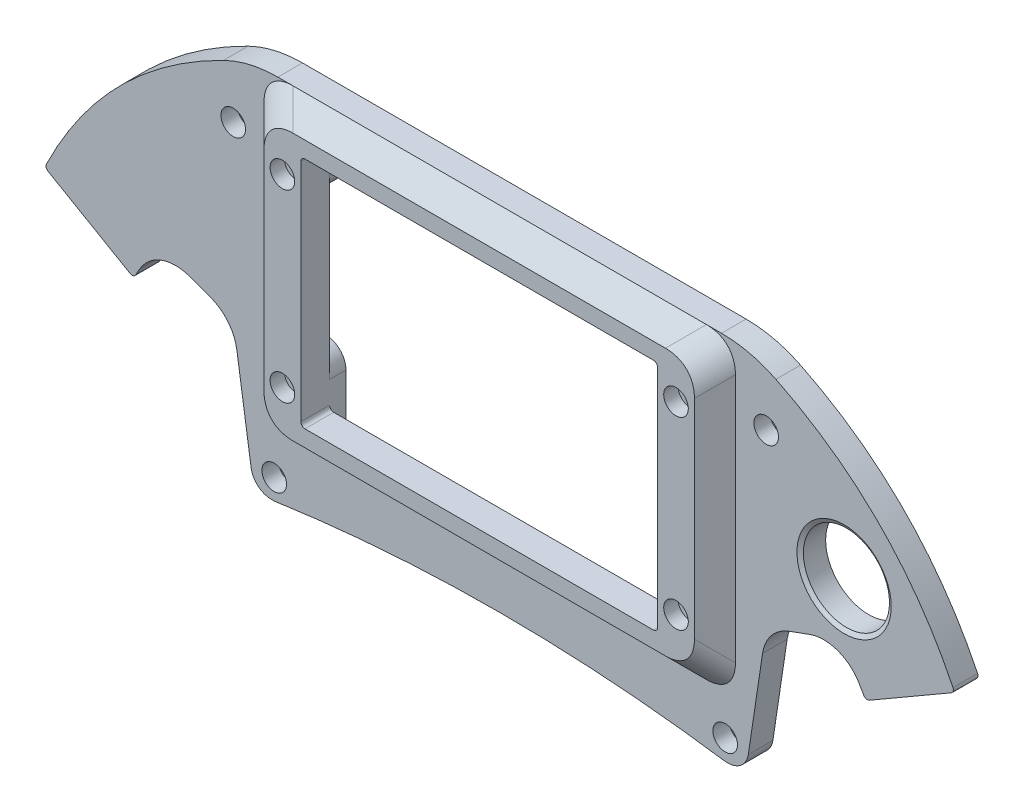
SolidWorks part; units mm, degrees
material "ABS"
ref_plane "正面" through (0, 0, 0) normal (0, 0, 1) x (1, 0, 0)
ref_plane "平面" through (0, 0, 0) normal (0, 1, 0) x (1, 0, 0)
ref_plane "右側面" through (0, 0, 0) normal (1, 0, 0) x (0, 0, -1)
sketch "ｽｹｯﾁ1" plane through (0, 0, 0) normal (0, 0, 1) x (1, 0, 0)
  line L1 (125, 105) -> (-125, 105) construction
  line L2 (125, 105) -> (125, -105) construction
  line L3 (125, -105) -> (-125, -105) construction
  line L4 (-125, 105) -> (-125, -105) construction
  line L5 (125, 105) -> (-125, -105) construction
  line L6 (125, -105) -> (-125, 105) construction
  circle A0 centre (0, 0) radius 125 construction
  point P0 (0, 0)
  dimension "D3" = 250
  dimension "D1" = 250
  dimension "D2" = 210
ref_plane "平面1" through (0, 0, 0) normal (0, 0, 1) x (1, 0, 0)
sketch "ｽｹｯﾁ2" plane through (0, 0, 0) normal (0, 0, 1) x (1, 0, 0)
  line L0 (0, 45) -> (-38.9711, -22.5) construction
  line L1 (-38.9711, -22.5) -> (38.9711, -22.5) construction
  line L2 (38.9711, -22.5) -> (0, 45) construction
  line L3 (-21.6506, 12.5) -> (21.6506, 12.5) construction
  line L4 (21.6506, 12.5) -> (0, -25) construction
  line L5 (0, -25) -> (-21.6506, 12.5) construction
  circle A0 centre (0, 0) radius 45 construction
  circle A1 centre (0, 0) radius 30 construction
  circle A2 centre (0, 0) radius 25 construction
  arc A3 (-29.9898, -0.784) -> (-15.6738, -25.5799) centre (-38.9711, -22.5) cw construction
  arc A4 (15.6738, -25.5799) -> (29.9898, -0.784) centre (38.9711, -22.5) cw construction
  arc A5 (-14.3159, 26.3639) -> (14.3159, 26.3639) centre (0, 45) ccw construction
  circle A6 centre (-21.6506, 12.5) radius 2.1 construction
  circle A7 centre (21.6506, 12.5) radius 2.1 construction
  circle A8 centre (0, -25) radius 2.1 construction
  dimension "D1" = 90
  dimension "D2" = 60
  dimension "D3" = 50
  dimension "D4" = 23.5
  dimension "D5" = 23.5
  dimension "D6" = 23.5
  dimension "D7" = 4.2
  dimension "D8" = 4.2
  dimension "D9" = 4.2
sketch "ｽｹｯﾁ3" plane through (0, 0, 0) normal (0, 0, 1) x (1, 0, 0)
  line L0 (-125, 105) -> (-125, -105) construction
  line L1 (125, 105) -> (125, -105) construction
  line L2 (-114.5644, 50) -> (114.5644, 50) construction
  line L3 (-105, -100) -> (-75, -100) construction
  line L4 (125, -105) -> (-125, -105) construction
  line L5 (0, 105) -> (0, -105) construction
  line L6 (125, 105) -> (-125, 105) construction
  line L7 (105, -100) -> (75, -100) construction
  arc A0 (-114.5644, 50) -> (-125, 0) centre (0, 0) ccw construction
  circle A1 centre (0, 0) radius 125 construction
  arc A2 (114.5644, 50) -> (125, 0) centre (0, 0) cw construction
  arc A3 (-95, 0) -> (-80.7775, 50) centre (0, 0) cw construction
  arc A4 (114.5644, 50) -> (125, 0) centre (0, 0) cw construction
  arc A5 (95, 0) -> (80.7775, 50) centre (0, 0) ccw construction
  spline S0 degree 3 poles (-125, 0) (-125, -34.2165) (-117.8201, -68.3401) (-105, -100) knots 0 0 0 0 1 1 1 1 construction
  spline S1 degree 3 poles (-75, -100) (-87.8201, -67.9365) (-95, -34.605) (-95, 0) knots 0 0 0 0 1 1 1 1 construction
  spline S2 degree 3 poles (125, 0) (125, -34.2165) (117.8201, -68.3401) (105, -100) knots 0 0 0 0 1 1 1 1 construction
  spline S3 degree 3 poles (75, -100) (87.8201, -67.9365) (95, -34.605) (95, 0) knots 0 0 0 0 1 1 1 1 construction
  point P12 (-120, -50)
  point P13 (-105, -100)
  point P18 (-90, -50)
  point P20 (-95, 0)
  dimension "D1" = 50
  dimension "D2" = 100
  dimension "D9" = 50
  dimension "D3" = 50
  dimension "D4" = 20
  dimension "D5" = 5
  dimension "D6" = 30
  dimension "D7" = 30
  dimension "D8" = 30
  dimension "D10" = 105
sketch "ｽｹｯﾁ4" plane through (0, 0, 0) normal (0, 0, 1) x (1, 0, 0)
  line L5 (125, -105) -> (-125, -105) construction
  line L8 (0, 105) -> (0, -105) construction
  line L10 (-125, 0) -> (125, 0) construction
  line L19 (0, -105) -> (0, 105) construction
  circle A0 centre (0, 0) radius 30 construction
  spline S2 degree 3 poles (-105, -100) (-71.8006, -85.9254) (0, -74.0746) (71.8006, -85.9254) (105, -100) knots 0 0 0 0 0.5 1 1 1 1 construction
  point P21 (-55, -85)
  point P22 (0, -80)
  point P23 (55, -85)
  point P58 (0, 30)
  dimension "D7" = 25
  dimension "D8" = 20
  dimension "D9" = 20
  dimension "D10" = 55
  dimension "D11" = 55
sketch "ｽｹｯﾁ5" plane through (0, 0, 0) normal (0, 0, 1) x (1, 0, 0)
  line L0 (-14.3159, 26.3639) -> (14.3159, 26.3639) construction
  circle A0 centre (0, 0) radius 100 construction
  dimension "D1" = 200
sketch "ｽｹｯﾁ6" plane through (0, 0, 0) normal (0, 0, 1) x (1, 0, 0)
  line L0 (0, -105) -> (0, 105) construction
  line L1 (-52.5, 98) -> (52.5, 98) construction
  line L2 (-52.5, 98) -> (-52.5, 28) construction
  line L3 (-52.5, 28) -> (52.5, 28) construction
  line L4 (52.5, 98) -> (52.5, 28) construction
  line L5 (-52.5, 98) -> (52.5, 28) construction
  line L6 (-52.5, 28) -> (52.5, 98) construction
  line L7 (125, 105) -> (-125, 105) construction
  point P0 (0, 63)
  dimension "D1" = 70
  dimension "D2" = 105
  dimension "D3" = 7
sketch "ｽｹｯﾁ7" plane through (0, 0, 0) normal (0, 0, 1) x (1, 0, 0)
  line L0 (-100, 0) -> (-60, 0) construction
  line L1 (-125, 0) -> (125, 0) construction
  line L2 (-98.8686, 15) -> (-60, 15) construction
  line L3 (-60, 15) -> (-65, 48.2606) construction
  line L4 (-65, 48.2606) -> (-83.5165, 55) construction
  line L5 (-60, 15) -> (-41.9606, -105) construction
  line L6 (125, -105) -> (-125, -105) construction
  line L7 (-60, -5) -> (-56.9934, -5) construction
  line L8 (-125, 105) -> (-125, -105) construction
  line L9 (-83.5165, 55) -> (-89.3029, 45) construction
  line L10 (-89.3029, 45) -> (-110.9703, 57.5377) construction
  line L11 (-110.9703, 57.5377) -> (-92.9863, 83.5377) construction
  line L12 (-92.9863, 83.5377) -> (-60.5, 105) construction
  line L13 (125, 105) -> (-125, 105) construction
  line L14 (-73.1949, -68.1359) -> (-48.3047, -62.7982) construction
  line L15 (-99.8749, -5) -> (-60, -5) construction
  line L16 (0, 0) -> (0, -30) construction
  line L17 (0, -105) -> (0, 105) construction
  line L18 (73.1949, -68.1359) -> (48.3047, -62.7982) construction
  line L19 (60, 15) -> (41.9606, -105) construction
  line L20 (60, -5) -> (56.9934, -5) construction
  line L21 (99.8749, -5) -> (60, -5) construction
  line L22 (98.8686, 15) -> (60, 15) construction
  line L23 (60, 15) -> (65, 48.2606) construction
  line L24 (65, 48.2606) -> (83.5165, 55) construction
  line L25 (83.5165, 55) -> (89.3029, 45) construction
  line L26 (89.3029, 45) -> (110.9703, 57.5377) construction
  line L27 (110.9703, 57.5377) -> (92.9863, 83.5377) construction
  line L28 (92.9863, 83.5377) -> (60.5, 105) construction
  circle A0 centre (0, 0) radius 100 construction
  circle A1 centre (0, 0) radius 125 construction
  arc A2 (-105, -100) -> (105, -100) centre (0, -348.7469) cw construction
  circle A3 centre (0, -348.7469) radius 270 construction
  circle A4 centre (0, -433.417) radius 132.7909 construction
  circle A5 centre (0, -348.7469) radius 290 construction
  circle A6 centre (0, 0) radius 30 construction
  spline S0 degree 3 poles (-105, -100) (-71.8006, -85.9254) (0, -74.0746) (71.8006, -85.9254) (105, -100) knots 0 0 0 0 0.5 1 1 1 1 construction
  dimension "D12" = 540
  dimension "D13" = 580
  dimension "D1" = 40
  dimension "D2" = 15
  dimension "D3" = 40
  dimension "D4" = 40
  dimension "D5" = 20
  dimension "D6" = 60
  dimension "D7" = 10
  dimension "D8" = 26
  dimension "D9" = 8
  dimension "D10" = 5
  dimension "D11" = 40
sketch "ｽｹｯﾁ8" plane through (0, 0, 0) normal (0, 0, 1) x (1, 0, 0)
  line L0 (-60, 15) -> (-65, 48.2606)
  line L1 (-65, 48.2606) -> (-83.5165, 55)
  line L2 (-83.5165, 55) -> (-89.3029, 45)
  line L3 (-89.3029, 45) -> (-110.9703, 57.5377)
  line L6 (-60.5, 105) -> (60.5, 105)
  line L9 (110.9703, 57.5377) -> (89.3029, 45)
  line L10 (89.3029, 45) -> (83.5165, 55)
  line L11 (83.5165, 55) -> (65, 48.2606)
  line L12 (65, 48.2606) -> (60, 15)
  line L13 (-60, 15) -> (-30, 10)
  line L14 (-30, 10) -> (30, 10) construction
  line L15 (-52.5, 98) -> (52.5, 28) construction
  line L16 (52.5, 98) -> (-52.5, 98)
  line L17 (52.5, 98) -> (52.5, 28)
  line L18 (52.5, 28) -> (-52.5, 28)
  line L19 (-52.5, 98) -> (-52.5, 28)
  line L20 (52.5, 98) -> (-52.5, 28) construction
  line L21 (52.5, 28) -> (-52.5, 98) construction
  line L22 (30, 10) -> (60, 15)
  line L23 (-125, 105) -> (-125, -105) construction
  line L24 (125, 105) -> (125, -105) construction
  line L25 (-125, 0) -> (125, 0) construction
  line L26 (-30, 10) -> (-26.6506, 10)
  line L27 (-26.6506, 10) -> (-26.6506, 12.5)
  line L28 (-16.6506, 12.5) -> (-16.6506, 10)
  line L29 (-16.6506, 10) -> (16.6506, 10)
  line L30 (16.6506, 10) -> (16.6506, 12.5)
  line L31 (26.6506, 12.5) -> (26.6506, 10)
  line L32 (26.6506, 10) -> (30, 10)
  circle A0 centre (-21.6506, 12.5) radius 5 construction
  circle A1 centre (21.6506, 12.5) radius 5 construction
  arc A2 (-26.6506, 12.5) -> (-16.6506, 12.5) centre (-21.6506, 12.5) cw
  arc A3 (16.6506, 12.5) -> (26.6506, 12.5) centre (21.6506, 12.5) cw
  spline S0 degree 2 poles (-110.9703, 57.5377) (-95.1002, 90.8355) (-60.5, 105) knots 0 0 0 1 1 1
  spline S1 degree 2 poles (110.9703, 57.5377) (95.1002, 90.8355) (60.5, 105) knots 0 0 0 1 1 1
  point P22 (0, 63)
  dimension "D4" = 10
  dimension "D5" = 10
  dimension "D1" = 95
  dimension "D2" = 95
  dimension "D3" = 10
extrude "ﾎﾞｽ - 押し出し1" add sketch "ｽｹｯﾁ8" along normal blind 6 contours L30 A3 L31 L32 L22 L12 L11 L10 L9 L6 L3 L2 L1 L0 L13 L26 L27 A2 L28 L29 L19 L16 L17 L18 region at (-60.1126, 31.9892, 0)
sketch "ｽｹｯﾁ9" plane through (0, 0, 6) normal (0, 0, 1) x (1, 0, 0)
  line L0 (-52.5, 73) -> (-46.5, 65.8495) construction
  line L1 (-52.5, 98) -> (-52.5, 28) construction
  line L2 (-46.5, 65.8495) -> (-46.5, 28) construction
  line L3 (-52.5, 28) -> (52.5, 28) construction
  line L4 (52.5, 73) -> (46.5, 65.8495) construction
  line L5 (52.5, 98) -> (52.5, 28) construction
  line L6 (46.5, 65.8495) -> (46.5, 28) construction
  dimension "D1" = 25
  dimension "D2" = 25
  dimension "D3" = 6
  dimension "D4" = 6
  dimension "D5" = 40
  dimension "D6" = 40
sketch "ｽｹｯﾁ11" plane through (0, 0, 6) normal (0, 0, 1) x (1, 0, 0)
  line L0 (0, -105) -> (0, 105) construction
  line L1 (-42.5, 95) -> (42.5, 95) construction
  line L2 (-42.5, 95) -> (-42.5, 40) construction
  line L3 (-42.5, 40) -> (42.5, 40) construction
  line L4 (42.5, 95) -> (42.5, 40) construction
  line L5 (-42.5, 95) -> (42.5, 40) construction
  line L6 (-42.5, 40) -> (42.5, 95) construction
  line L7 (-52.5, 28) -> (52.5, 28) construction
  line L9 (0, 26) -> (-54.5, 26) construction
  line L10 (-54.5, 26) -> (-54.5, 100) construction
  line L11 (-54.5, 100) -> (54.5, 100) construction
  line L12 (54.5, 100) -> (54.5, 26) construction
  line L13 (54.5, 26) -> (0, 26) construction
  line L14 (-52.5, 98) -> (-52.5, 28) construction
  line L15 (-52.5, 98) -> (52.5, 98) construction
  line L16 (52.5, 98) -> (52.5, 28) construction
  point P0 (0, 67.5)
  dimension "D1" = 85
  dimension "D2" = 55
  dimension "D3" = 3
  dimension "D4" = 2
  dimension "D5" = 2
  dimension "D6" = 2
  dimension "D7" = 2
sketch "ｽｹｯﾁ12" plane through (0, 0, 6) normal (0, 0, 1) x (1, 0, 0)
  line L0 (-42.5, 40) -> (42.5, 40)
  line L1 (42.5, 40) -> (42.5, 95)
  line L2 (42.5, 95) -> (-42.5, 95)
  line L3 (-42.5, 95) -> (-42.5, 40)
  line L4 (-54.5, 26) -> (54.5, 26)
  line L5 (54.5, 26) -> (54.5, 100)
  line L6 (54.5, 100) -> (-54.5, 100)
  line L7 (-54.5, 100) -> (-54.5, 26)
extrude "ﾎﾞｽ - 押し出し2" add sketch "ｽｹｯﾁ12" along normal blind 7 and the other way blind 2
sketch "ｽｹｯﾁ13" plane through (0, 0, 13) normal (0, 0, 1) x (1, 0, 0)
  line L1 (-58.5, 77.0391) -> (-58.5, 25.0391)
  line L2 (-58.5, 25.0391) -> (-48.5, 25.0391)
  line L5 (58.5, 77.0391) -> (58.5, 25.0391)
  line L6 (58.5, 25.0391) -> (48.5, 25.0391)
  line L11 (58.5, 77.0391) -> (48.5, 65.1215)
  line L12 (48.5, 65.1215) -> (48.5, 25.0391)
  line L13 (52.5, 73) -> (46.5, 65.8495) construction
  line L15 (46.5, 65.8495) -> (46.5, 28) construction
  line L16 (-58.5, 77.0391) -> (-48.5, 65.1215)
  line L17 (-48.5, 65.1215) -> (-48.5, 25.0391)
  line L18 (-52.5, 73) -> (-46.5, 65.8495) construction
  line L20 (-46.5, 65.8495) -> (-46.5, 28) construction
  point P14 (49.5, 69.4247)
  dimension "D1" = 2
  dimension "D2" = 52
  dimension "D3" = 10
  dimension "D4" = 52
  dimension "D5" = 2
  dimension "D6" = 2
  dimension "D7" = 2
  dimension "D8" = 10
extrude "ｶｯﾄ - 押し出し1" cut sketch "ｽｹｯﾁ13" against normal blind 7
sketch "ｽｹｯﾁ14" plane through (0, 0, 0) normal (0, 0, 1) x (1, 0, 0)
  line L0 (-52.5, 98) -> (52.5, 98) construction
  line L1 (-52.5, 98) -> (-52.5, 28) construction
  line L3 (0, 67.5) -> (0, 46.8637) construction
  line L4 (-42.5, 95) -> (42.5, 40) construction
  line L5 (0, -105) -> (0, 105) construction
  circle A0 centre (-48.5, 76) radius 3 construction
  circle A2 centre (48.5, 76) radius 3 construction
  circle A3 centre (48.5, 76) radius 1.75
  circle A4 centre (-48.5, 76) radius 1.75
  dimension "D1" = 6
  dimension "D4" = 3.5
  dimension "D5" = 3.5
  dimension "D2" = 22
  dimension "D3" = 4
sketch "ｽｹｯﾁ15" plane through (0, 0, 4) normal (0, 0, -1) x (-1, 0, 0)
  line L0 (-52.5, 80) -> (-43.5, 80)
  line L1 (-52.5, 98) -> (-52.5, 28) construction
  line L2 (-43.5, 80) -> (-43.5, 72)
  line L5 (-43.5, 72) -> (-51.6609, 72)
  line L6 (-52.5, 73) -> (-46.5, 65.8495) construction
  line L7 (-51.6609, 72) -> (-46.5, 65.8495)
  line L8 (-46.5, 65.8495) -> (-46.5, 28)
  line L9 (-46.5, 28) -> (46.5, 28)
  line L10 (46.5, 28) -> (46.5, 65.8495)
  line L11 (46.5, 65.8495) -> (51.6609, 72)
  line L12 (52.5, 73) -> (46.5, 65.8495) construction
  line L13 (51.6609, 72) -> (42.5, 72)
  line L14 (42.5, 72) -> (42.5, 80)
  line L15 (42.5, 80) -> (52.5, 80)
  line L16 (52.5, 98) -> (52.5, 28) construction
  line L17 (42.5, 95) -> (42.5, 40) construction
  line L18 (52.5, 80) -> (52.5, 98)
  line L19 (52.5, 98) -> (-52.5, 98)
  line L20 (-52.5, 98) -> (-52.5, 80)
  circle A0 centre (-48.5, 76) radius 3 construction
  dimension "D1" = 4
  dimension "D2" = 4
  dimension "D3" = 5
  dimension "D4" = 8
  dimension "D5" = 4
extrude "ｶｯﾄ - 押し出し2" cut sketch "ｽｹｯﾁ15" against normal blind 7
extrude "ｶｯﾄ - 押し出し4" cut sketch "ｽｹｯﾁ14" along normal blind 100
sketch "ｽｹｯﾁ16" plane through (0, 0, 13) normal (0, 0, 1) x (1, 0, 0)
  circle A0 centre (48.5, 76) radius 3
  circle A1 centre (-48.5, 76) radius 3
  dimension "D1" = 6
  dimension "D2" = 6
extrude "ｶｯﾄ - 押し出し5" cut sketch "ｽｹｯﾁ16" against normal blind 3.5
sketch "ｽｹｯﾁ17" plane through (0, 0, 4) normal (0, 0, -1) x (-1, 0, 0)
  line L0 (-43.5, 72) -> (-52.5, 72)
  line L1 (-52.5, 98) -> (-52.5, 28) construction
  line L2 (-52.5, 72) -> (-52.5, 80)
  line L3 (-52.5, 80) -> (-43.5, 80)
  line L6 (43.5, 72) -> (52.5, 72)
  line L7 (52.5, 98) -> (52.5, 28) construction
  line L8 (52.5, 72) -> (52.5, 80)
  line L9 (52.5, 80) -> (43.5, 80)
  line L10 (-43.5, 72) -> (-51.6609, 72) construction
  line L11 (-43.5, 80) -> (-43.5, 72)
  line L12 (-43.5, 80) -> (-43.5, 72) construction
  line L14 (51.6609, 72) -> (42.5, 72) construction
  line L15 (42.5, 80) -> (52.5, 80) construction
  line L16 (43.5, 80) -> (43.5, 72)
  dimension "D1" = 9
extrude "ｶｯﾄ - 押し出し6" cut sketch "ｽｹｯﾁ17" against normal blind 3
sketch "ｽｹｯﾁ18" plane through (0, 0, 11) normal (0, 0, -1) x (-1, 0, 0)
  line L0 (52.5, 98) -> (-52.5, 98) construction
  line L1 (-52.5, 98) -> (-52.5, 28) construction
  circle A0 centre (-41.25, 92) radius 2.6
  circle A1 centre (-33.75, 92) radius 2.6
  circle A2 centre (-26.25, 92) radius 2.6
  circle A3 centre (-18.75, 92) radius 2.6
  circle A4 centre (-11.25, 92) radius 2.6
  circle A5 centre (-3.75, 92) radius 2.6
  circle A6 centre (3.75, 92) radius 2.6
  circle A7 centre (11.25, 92) radius 2.6
  circle A8 centre (18.75, 92) radius 2.6
  circle A9 centre (26.25, 92) radius 2.6
  circle A10 centre (33.75, 92) radius 2.6
  circle A11 centre (41.25, 92) radius 2.6
  dimension "D1" = 5.2
  dimension "D3" = 11.25
  dimension "D2" = 6
  dimension "D4" = 12
extrude "ｶｯﾄ - 押し出し7" cut sketch "ｽｹｯﾁ18" against normal blind 3
sketch "ｽｹｯﾁ19" plane through (0, 0, 6) normal (0, 0, 1) x (1, 0, 0)
  line L1 (-125, 0) -> (125, 0) construction
  line L2 (0, -105) -> (0, 105) construction
  circle A0 centre (84, 68) radius 10.5 construction
  dimension "D1" = 21
  dimension "D3" = 84
  dimension "D2" = 68
sketch "ｽｹｯﾁ21" plane through (0, 0, 6) normal (0, 0, 1) x (1, 0, 0)
  line L0 (83.0683, 57.5414) -> (83.5165, 55)
  line L1 (65, 48.2606) -> (83.5165, 55) construction
  line L2 (83.5165, 55) -> (86.3919, 42.8329)
  line L3 (86.3919, 42.8329) -> (125.4665, 52.0672)
  line L4 (125.4665, 52.0672) -> (98.7771, 79.0548)
  line L5 (98.7771, 79.0548) -> (92.6692, 73.9241)
  line L6 (125, 105) -> (-125, -105) construction
  arc A0 (83.0683, 57.5414) -> (92.6692, 73.9241) centre (84, 68) cw
  circle A1 centre (84, 68) radius 10.5 construction
  dimension "D1" = 100
  dimension "D2" = 3
sketch "ｽｹｯﾁ22" plane through (0, 0, 6) normal (0, 0, 1) x (1, 0, 0)
  circle A0 centre (84, 68) radius 10.5
  dimension "D1" = 21
sketch "ｽｹｯﾁ25" plane through (0, 0, 4) normal (0, 0, -1) x (-1, 0, 0)
  line L0 (42.5, 80) -> (43.5, 80)
  line L1 (42.5, 80) -> (43.5, 80) construction
  line L2 (43.5, 80) -> (43.5, 72)
  line L3 (43.5, 80) -> (43.5, 72) construction
  line L4 (43.5, 72) -> (42.5, 72)
  line L5 (42.5, 72) -> (42.5, 80)
extrude "ｶｯﾄ - 押し出し14" cut sketch "ｽｹｯﾁ25" against normal blind 7
sketch "ｽｹｯﾁ26" plane through (0, 0, 13) normal (0, 0, 1) x (1, 0, 0)
  line L1 (43.5, 96) -> (-43.5, 96)
  line L2 (43.5, 96) -> (43.5, 39)
  line L3 (43.5, 39) -> (-43.5, 39)
  line L4 (-43.5, 96) -> (-43.5, 39)
  line L5 (43.5, 96) -> (-43.5, 39) construction
  line L6 (43.5, 39) -> (-43.5, 96) construction
  point P0 (0, 67.5)
  dimension "D1" = 57
  dimension "D2" = 87
extrude "ｶｯﾄ - 押し出し15" cut sketch "ｽｹｯﾁ26" against normal blind 7
sketch "ｽｹｯﾁ27" plane through (0, 0, 4) normal (0, 0, -1) x (-1, 0, 0)
  line L0 (-52.5, 72) -> (-51.6609, 72)
  line L1 (-51.6609, 72) -> (-46.5, 65.8495)
  line L2 (-46.5, 65.8495) -> (-46.5, 28)
  line L3 (-46.5, 28) -> (-52.5, 28)
  line L5 (0, 30) -> (0, 45) construction
  line L6 (-52.5, 28) -> (-52.5, 72)
  line L7 (46.5, 28) -> (52.5, 28)
  line L8 (46.5, 65.8495) -> (46.5, 28)
  line L9 (51.6609, 72) -> (46.5, 65.8495)
  line L10 (52.5, 72) -> (51.6609, 72)
  line L11 (52.5, 28) -> (52.5, 72)
extrude "ﾎﾞｽ - 押し出し3" add sketch "ｽｹｯﾁ27" along normal blind 6
sketch "ｽｹｯﾁ29" plane through (0, 0, 6) normal (0, 0, 1) x (1, 0, 0)
  line L0 (125, 105) -> (-125, 105) construction
  line L1 (0, -105) -> (0, 105) construction
  line L2 (0, 67.5) -> (0, 26.3639) construction
  line L3 (-14.3159, 26.3639) -> (14.3159, 26.3639) construction
  circle A0 centre (-65, 90) radius 1.5 construction
  circle A1 centre (-55, 20) radius 1.5 construction
  circle A2 centre (65, 90) radius 1.5 construction
  circle A3 centre (55, 20) radius 1.5 construction
  dimension "D1" = 3
  dimension "D2" = 15
  dimension "D3" = 65
  dimension "D4" = 3
  dimension "D5" = 55
  dimension "D6" = 85
sketch "ｽｹｯﾁ30" plane through (0, 0, 6) normal (0, 0, 1) x (1, 0, 0)
  line L0 (0, 67.5) -> (0, 30) construction
  line L1 (-42.5, 40) -> (42.5, 95) construction
  circle A0 centre (-65, 90) radius 3
  circle A1 centre (-55, 20) radius 3
  circle A2 centre (55, 20) radius 3
  circle A3 centre (65, 90) radius 3
  dimension "D1" = 6
  dimension "D2" = 6
extrude "ｶｯﾄ - 押し出し16" cut sketch "ｽｹｯﾁ30" against normal blind 4
sketch "ｽｹｯﾁ31" plane through (0, 0, 6) normal (0, 0, 1) x (1, 0, 0)
  line L0 (0, 67.5) -> (0, 26) construction
  circle A0 centre (-65, 90) radius 1.75
  circle A1 centre (-55, 20) radius 1.75
  circle A2 centre (55, 20) radius 1.75
  circle A3 centre (65, 90) radius 1.75
  dimension "D1" = 3.5
  dimension "D2" = 3.5
extrude "ｶｯﾄ - 押し出し17" cut sketch "ｽｹｯﾁ31" against normal blind 50
sketch "ｽｹｯﾁ33" plane through (0, 0, 0) normal (0, 0, -1) x (-1, 0, 0)
  line L0 (106.6531, 58.5056) -> (90.5191, 81.8311)
  line L2 (84.8536, 58.6792) -> (90.397, 49.0991)
  line L3 (90.397, 49.0991) -> (106.6531, 58.5056)
  line L6 (83.5, 84) -> (57.5, 84)
  line L7 (57.5, 84) -> (57.5, 50.4323)
  line L8 (89.3029, 45) -> (110.9703, 57.5377) construction
  line L9 (83.5165, 55) -> (89.3029, 45) construction
  line L13 (90.5191, 81.8311) -> (83.5, 84)
  line L14 (52.5, 98) -> (52.5, 72) construction
  line L16 (84.8536, 58.6792) -> (62.1954, 50.4323)
  line L17 (62.1954, 50.4323) -> (57.5, 50.4323)
  line L18 (65, 48.2606) -> (83.5165, 55) construction
  line L19 (54.5, 26) -> (54.5, 100) construction
  line L20 (110.9703, 57.5377) -> (92.9863, 83.5377) construction
  line L21 (89.3029, 45) -> (110.9703, 57.5377) construction
  circle A2 centre (65, 90) radius 1.75 construction
  dimension "D1" = 6
  dimension "D2" = 3
  dimension "D3" = 3
  dimension "D4" = 3
  dimension "D5" = 3
  dimension "D6" = 3
  dimension "D7" = 3
  dimension "D8" = 26
sketch "ｽｹｯﾁ36" plane through (0, 0, 0) normal (0, 0, -1) x (-1, 0, 0)
  line L0 (-57.5, 50) -> (-57.5, 84)
  line L3 (-77.6828, 56.0692) -> (-61.0077, 50)
  line L4 (-61.0077, 50) -> (-57.5, 50)
  line L5 (-65, 48.2606) -> (-83.5165, 55) construction
  line L7 (-80.3599, 81) -> (-80.3599, 84)
  line L8 (-54.5, 100) -> (-54.5, 26) construction
  line L9 (-80.3599, 84) -> (-57.5, 84)
  line L10 (-98.8686, 15) -> (-60, 15) construction
  arc A0 (-80.3599, 81) -> (-77.6828, 56.0692) centre (-84, 68) cw
  circle A2 centre (-84, 68) radius 10.5 construction
  dimension "D1" = 3
  dimension "D4" = 6
  dimension "D3" = 3
  dimension "D2" = 3
  dimension "D5" = 3
  dimension "D6" = 35
sketch "ｽｹｯﾁ37" plane through (0, 0, 6) normal (0, 0, 1) x (1, 0, 0)
  line L0 (-60, 15) -> (-30, 15)
  line L1 (-30, 15) -> (-28.5566, 17.5)
  line L2 (-28.5566, 17.5) -> (28.5566, 17.5)
  line L3 (0, -105) -> (0, 105) construction
  line L4 (0, 17.5) -> (0, 0) construction
  line L5 (60, 0) -> (-60, 0)
  line L6 (-60, 0) -> (-60, 15)
  line L7 (30, 15) -> (28.5566, 17.5)
  line L8 (60, 15) -> (30, 15)
  line L9 (60, 0) -> (60, 15)
  arc A1 (-16.6506, 12.5) -> (-26.6506, 12.5) centre (-21.6506, 12.5) ccw construction
  dimension "D1" = 30
  dimension "D2" = 120
extrude "ｶｯﾄ - 押し出し18" cut sketch "ｽｹｯﾁ37" against normal blind 10
sketch "ｽｹｯﾁ38" plane through (0, 0, 6) normal (0, 0, 1) x (1, 0, 0)
  line L1 (153.4339, 129.5916) -> (-153.4339, 129.5916)
  line L2 (153.4339, 129.5916) -> (153.4339, 5.4084)
  line L3 (153.4339, 5.4084) -> (-153.4339, 5.4084)
  line L4 (-153.4339, 129.5916) -> (-153.4339, 5.4084)
  line L5 (153.4339, 129.5916) -> (-153.4339, 5.4084) construction
  line L6 (153.4339, 5.4084) -> (-153.4339, 129.5916) construction
  point P0 (0, 67.5)
extrude "ｶｯﾄ - 押し出し19" cut sketch "ｽｹｯﾁ38" along normal blind 10
sketch "ｽｹｯﾁ39" plane through (0, 0, 6) normal (0, 0, 1) x (1, 0, 0)
  line L0 (-52.5, 98) -> (52.5, 98)
  line L1 (52.5, 98) -> (52.5, 28)
  line L2 (52.5, 28) -> (-52.5, 28)
  line L3 (-52.5, 28) -> (-52.5, 98)
extrude "ﾎﾞｽ - 押し出し4" add sketch "ｽｹｯﾁ39" against normal blind 8
sketch "ｽｹｯﾁ40" plane through (0, 0, 6) normal (0, 0, 1) x (1, 0, 0)
  line L0 (0, -105) -> (0, 105) construction
  line L1 (52.5, 100) -> (-52.5, 100)
  line L2 (52.5, 100) -> (52.5, 35)
  line L3 (52.5, 35) -> (-52.5, 35)
  line L4 (-52.5, 100) -> (-52.5, 35)
  line L5 (52.5, 100) -> (-52.5, 35) construction
  line L6 (52.5, 35) -> (-52.5, 100) construction
  line L11 (-42.5, 40) -> (42.5, 40) construction
  point P0 (0, 67.5)
  dimension "D1" = 105
  dimension "D2" = 65
  dimension "D3" = 5
sketch "ｽｹｯﾁ42" plane through (0, 0, 6) normal (0, 0, 1) x (1, 0, 0)
  line L0 (0, -105) -> (0, 105) construction
  line L1 (-57.5, 105) -> (57.5, 105)
  line L2 (-57.5, 105) -> (-57.5, 30)
  line L3 (-57.5, 30) -> (57.5, 30)
  line L4 (57.5, 105) -> (57.5, 30)
  line L5 (-57.5, 105) -> (57.5, 30) construction
  line L6 (-57.5, 30) -> (57.5, 105) construction
  line L7 (125, 105) -> (-125, 105) construction
  line L9 (52.5, 35) -> (-52.5, 35) construction
  point P0 (0, 67.5)
  dimension "D1" = 115
  dimension "D2" = 5
ref_plane "平面2" through (0, 0, 11) normal (0, 0, 1) x (1, 0, 0)
sketch "ｽｹｯﾁ43" plane through (0, 0, 11) normal (0, 0, 1) x (1, 0, 0)
  line L0 (-57.5, 105) -> (57.5, 30) construction
  line L1 (52.5, 100) -> (-52.5, 100)
  line L2 (52.5, 100) -> (52.5, 35)
  line L3 (52.5, 35) -> (-52.5, 35)
  line L4 (-52.5, 100) -> (-52.5, 35)
  line L5 (52.5, 100) -> (-52.5, 35) construction
  line L6 (52.5, 35) -> (-52.5, 100) construction
  point P0 (0, 67.5)
  dimension "D1" = 105
  dimension "D2" = 65
loft "ﾛﾌﾄ1" add profiles "ｽｹｯﾁ43", "ｽｹｯﾁ42" connector at (-52.5, 100, 11) connector at (-57.5, 105, 6)
fillet "ﾌｨﾚｯﾄ1" radius 10 4 edges
sketch "ｽｹｯﾁ44" plane through (0, 0, 11) normal (0, 0, 1) x (1, 0, 0)
  line L1 (43.5, 96) -> (-43.5, 96)
  line L2 (43.5, 96) -> (43.5, 39)
  line L3 (43.5, 39) -> (-43.5, 39)
  line L4 (-43.5, 96) -> (-43.5, 39)
  line L5 (43.5, 96) -> (-43.5, 39) construction
  line L6 (43.5, 39) -> (-43.5, 96) construction
  point P0 (0, 67.5)
  dimension "D1" = 87
  dimension "D2" = 57
extrude "ｶｯﾄ - 押し出し21" cut sketch "ｽｹｯﾁ44" against normal through all
sketch "ｽｹｯﾁ45" plane through (0, 0, 0) normal (0, 0, 1) x (1, 0, 0)
  line L0 (-48, 90) -> (-48, 45) construction
  line L2 (-43.5, 96) -> (-43.5, 39) construction
  line L3 (-54.5, 100) -> (54.5, 100) construction
  line L4 (52.5, 35) -> (-52.5, 35) construction
  line L5 (0, 105) -> (0, 30) construction
  circle A0 centre (-48, 90) radius 1.75
  circle A1 centre (-48, 45) radius 1.75
  circle A2 centre (48, 45) radius 1.75
  circle A3 centre (48, 90) radius 1.75
  dimension "D1" = 3.5
  dimension "D2" = 3.5
  dimension "D4" = 10
  dimension "D5" = 10
  dimension "D3" = 4.5
extrude "ｶｯﾄ - 押し出し23" cut sketch "ｽｹｯﾁ45" along normal through all
sketch "ｽｹｯﾁ46" plane through (0, 0, 11) normal (0, 0, 1) x (1, 0, 0)
  line L0 (0, 105) -> (0, 30) construction
  line L1 (125, 105) -> (-125, 105) construction
  circle A0 centre (-48, 90) radius 3
  circle A1 centre (-48, 45) radius 3
  circle A2 centre (48, 45) radius 3
  circle A3 centre (48, 90) radius 3
  dimension "D1" = 6
  dimension "D2" = 6
extrude "ｶｯﾄ - 押し出し24" cut sketch "ｽｹｯﾁ46" against normal blind 3.5
sketch "ｽｹｯﾁ47" plane through (0, 0, 0) normal (0, 0, -1) x (-1, 0, 0)
  circle A0 centre (-84, 68) radius 10.5
  dimension "D1" = 21
extrude "ｶｯﾄ - 押し出し25" cut sketch "ｽｹｯﾁ47" against normal through all
sketch "ｽｹｯﾁ48" plane through (0, 0, 0) normal (0, 0, -1) x (-1, 0, 0)
  line L0 (-84, 80.5) -> (-84, 84)
  line L1 (-84, 84) -> (-43.5, 84)
  line L2 (-43.5, 39) -> (-43.5, 96) construction
  line L3 (-43.5, 84) -> (-43.5, 51)
  line L4 (-43.5, 51) -> (-63.7551, 51)
  line L5 (-63.7551, 51) -> (-78.9936, 56.5463)
  line L6 (-65, 48.2606) -> (-83.5165, 55) construction
  line L7 (43.5, 84) -> (83.5, 84)
  line L8 (43.5, 96) -> (43.5, 39) construction
  line L9 (83.5, 84) -> (90.5191, 81.8311)
  line L10 (90.5191, 81.8311) -> (106.6531, 58.5056)
  line L11 (106.6531, 58.5056) -> (90.397, 49.0991)
  line L12 (90.397, 49.0991) -> (84.8536, 58.6792)
  line L13 (84.8536, 58.6792) -> (62.1954, 50.4323)
  line L14 (62.1954, 50.4323) -> (57.5, 50.4323)
  line L15 (43.5, 50.4323) -> (43.5, 84)
  line L16 (43.5, 50.4323) -> (57.5, 50.4323)
  arc A0 (-84, 80.5) -> (-78.9936, 56.5463) centre (-84, 68) cw
  circle A1 centre (-48, 45) radius 1.75 construction
  circle A2 centre (-48, 90) radius 1.75 construction
  dimension "D1" = 12.5
  dimension "D2" = 6
  dimension "D3" = 6
  dimension "D4" = 3
extrude "ｶｯﾄ - 押し出し26" cut sketch "ｽｹｯﾁ48" against normal blind 4
sketch "ｽｹｯﾁ49" plane through (0, 0, 0) normal (0, 0, -1) x (-1, 0, 0)
  line L0 (-43.5, 96) -> (-43.5, 101)
  line L1 (-43.5, 101) -> (43.5, 101)
  line L2 (43.5, 101) -> (43.5, 21.5)
  line L3 (43.5, 21.5) -> (-43.5, 21.5)
  line L4 (-43.5, 21.5) -> (-43.5, 96)
  line L6 (-125, 105) -> (125, 105) construction
  line L7 (-28.5566, 17.5) -> (28.5566, 17.5) construction
  line L8 (43.5, 96) -> (43.5, 84) construction
  dimension "D1" = 4
  dimension "D2" = 4
extrude "ｶｯﾄ - 押し出し27" cut sketch "ｽｹｯﾁ49" against normal blind 4
fillet "ﾌｨﾚｯﾄ2" radius 30 2 edges at (60.5, 105, 3) (-60.5, 105, 3)
fillet "ﾌｨﾚｯﾄ3" radius 10 4 edges at (83.5165, 55, 3) (65, 48.2606, 3) (-65, 48.2606, 3) (-83.5165, 55, 3)
fillet "ﾌｨﾚｯﾄ4" radius 1 8 edges at (110.9703, 57.5377, 3) (89.3029, 45, 3) (-89.3029, 45, 3) (-110.9703, 57.5377, 3) (43.5, 96, 7.5) (43.5, 39, 7.5) (-43.5, 39, 7.5) (-43.5, 96, 7.5)
fillet "ﾌｨﾚｯﾄ5" radius 5 10 edges at (43.5, 21.5, 2) (-43.5, 21.5, 2) (-43.5, 101, 2) (43.5, 101, 2) (-43.5, 50.4323, 2) (-43.5, 84, 2) (43.5, 51, 2) (43.5, 84, 2) (-60, 15, 3) (60, 15, 3)
fillet "ﾌｨﾚｯﾄ7" radius 1 4 edges at (30, 15, 3) (28.5566, 17.5, 3) (-28.5566, 17.5, 3) (-30, 15, 3)
fillet "ﾌｨﾚｯﾄ8" radius 10 1 edges at (-84.8536, 58.6792, 2)
sketch "ｽｹｯﾁ50" plane through (0, 0, 11) normal (0, 0, 1) x (1, 0, 0)
  line L0 (-48, 90) -> (48, 90) construction
sketch "ｽｹｯﾁ51" plane through (0, 0, 11) normal (0, 0, 1) x (1, 0, 0)
  line L0 (-48, 90) -> (-48, 45) construction
sketch "ｽｹｯﾁ52" plane through (0, 0, 0) normal (0, 0, -1) x (-1, 0, 0)
  circle A0 centre (-84, 68) radius 8
  circle A1 centre (-84, 68) radius 10.5
  dimension "D1" = 16
sketch "ｽｹｯﾁ53" plane through (0, 0, 6) normal (0, 0, 1) x (1, 0, 0)
  line L0 (-30.5774, 15) -> (-55.6955, 15) construction
  line L1 (0, -105) -> (0, 105) construction
  line L2 (-55, 15) -> (55, 15)
  line L3 (0, 15) -> (0, 18.9765) construction
  spline S0 degree 3 poles (-55, 15) (-36.7696, 17.6474) (-18.4362, 18.9765) (0, 18.9765) knots 0 0 0 0 1 1 1 1
  spline S1 degree 3 poles (55, 15) (36.7696, 17.6474) (18.4362, 18.9765) (0, 18.9765) knots 0 0 0 0 1 1 1 1
  dimension "D1" = 5
extrude "ｶｯﾄ - 押し出し28" cut sketch "ｽｹｯﾁ53" against normal blind 15
sketch "ｽｹｯﾁ54" plane through (0, 0, 0) normal (0, 0, 1) x (1, 0, 0)
  line L0 (0, -105) -> (0, 105) construction
  line L1 (52.5, 96) -> (-52.5, 96)
  line L2 (52.5, 96) -> (52.5, 31)
  line L3 (52.5, 31) -> (-52.5, 31)
  line L4 (-52.5, 96) -> (-52.5, 31)
  line L5 (52.5, 96) -> (-52.5, 31) construction
  line L6 (52.5, 31) -> (-52.5, 96) construction
  line L7 (42.5, 96) -> (-42.5, 96) construction
  line L8 (42.5, 95) -> (-42.5, 95)
  line L9 (42.5, 95) -> (42.5, 40)
  line L10 (42.5, 40) -> (-42.5, 40)
  line L11 (-42.5, 95) -> (-42.5, 40)
  line L12 (42.5, 95) -> (-42.5, 40) construction
  line L13 (42.5, 40) -> (-42.5, 95) construction
  circle A0 centre (-48, 90) radius 3
  circle A1 centre (48, 90) radius 3
  point P0 (0, 63.5)
  point P7 (0, 67.5)
  dimension "D1" = 65
  dimension "D2" = 105
  dimension "D3" = 55
  dimension "D4" = 85
  dimension "D5" = 1
  dimension "D6" = 1
sketch "ｽｹｯﾁ55" plane through (0, 0, 0) normal (0, 0, -1) x (-1, 0, 0)
  line L1 (78.4089, 120.4752) -> (-73.5652, 120.4752)
  line L2 (78.4089, 120.4752) -> (78.4089, 11.279)
  line L3 (78.4089, 11.279) -> (-73.5652, 11.279)
  line L4 (-73.5652, 120.4752) -> (-73.5652, 11.279)
  line L5 (78.4089, 120.4752) -> (-73.5652, 11.279) construction
  line L6 (78.4089, 11.279) -> (-73.5652, 120.4752) construction
  point P0 (2.4218, 65.8771)
extrude "ｶｯﾄ - 押し出し29" cut sketch "ｽｹｯﾁ55" along normal blind 10
chamfer "面取り1" distance 1 angle 30 1 edges at (94.5, 68, 6) first distance on face at (0.0256, 52.3329, 6)
